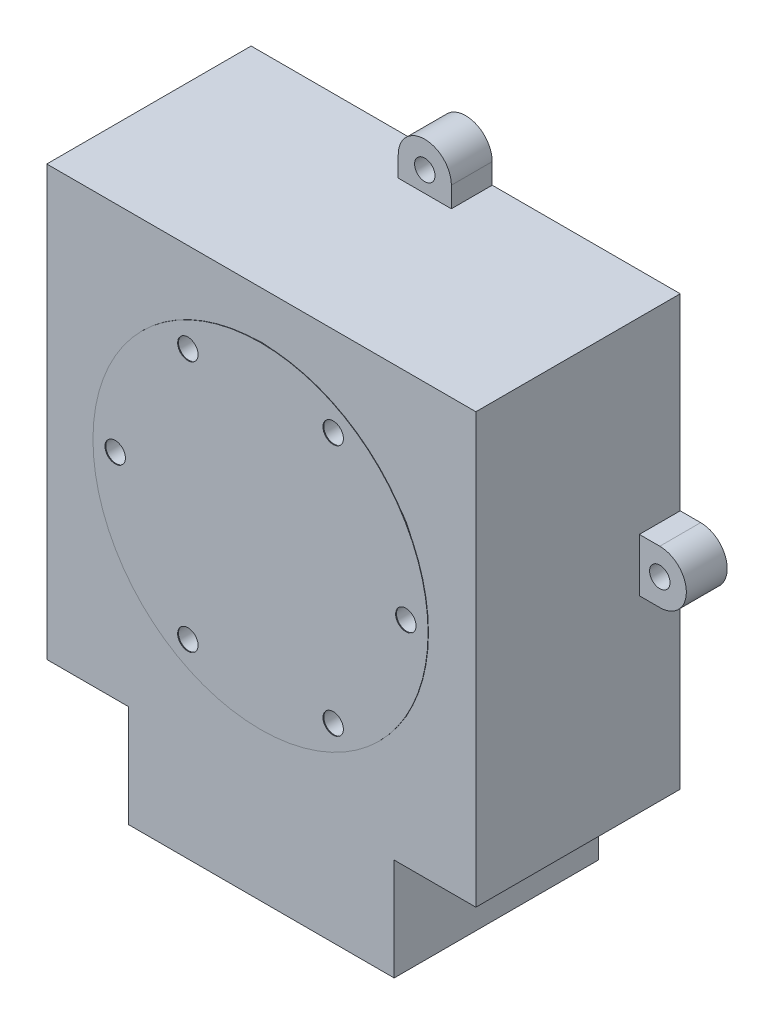
SolidWorks part; units mm, degrees
ref_plane "Front Plane" through (0, 0, 0) normal (0, 0, 1) x (1, 0, 0)
ref_plane "Top Plane" through (0, 0, 0) normal (0, 1, 0) x (1, 0, 0)
ref_plane "Right Plane" through (0, 0, 0) normal (1, 0, 0) x (0, 0, -1)
sketch "Sketch1" plane through (0, 0, 0) normal (0, 0, 1) x (1, 0, 0)
  circle A0 centre (0, 0) radius 41
  dimension "D1" = 82
extrude "Boss-Extrude1" add sketch "Sketch1" along normal blind 0.1 contours A0
sketch "Sketch2" plane through (0, 0, 0) normal (0, 0, -1) x (-1, 0, 0)
  line L0 (-35.56, 0) -> (35.56, 0) construction
  line L1 (0, 0) -> (0, -41) construction
  line L2 (0, 0) -> (0, 41) construction
  line L3 (0, -30.7959) -> (17.78, -30.7959) construction
  line L4 (0, -30.7959) -> (-17.78, -30.7959) construction
  circle A0 centre (-35.56, 0) radius 2.5
  circle A1 centre (35.56, 0) radius 2.5
  circle A2 centre (0, 0) radius 38.06 construction
  circle A3 centre (0, 0) radius 33.06 construction
  circle A4 centre (-17.78, -30.7959) radius 2.5
  circle A5 centre (17.78, -30.7959) radius 2.5
  circle A6 centre (0, 0) radius 41 construction
  circle A7 centre (-17.78, 30.7959) radius 2.5
  circle A8 centre (17.78, 30.7959) radius 2.5
  point P4 (0, 0)
  dimension "D2" = 5
  dimension "D3" = 66.12
  dimension "D4" = 76.12
  dimension "D6" = 5
  dimension "D7" = 5
  dimension "D1" = 71.12
  dimension "D5" = 35.56
extrude "Cut-Extrude1" cut sketch "Sketch2" against normal blind 10
sketch "Sketch3" plane through (0, 0, 0) normal (0, 0, -1) x (-1, 0, 0)
  circle A1 centre (0, 0) radius 47.5 construction
  arc A2 (22.2693, -27.7235) -> (12.8746, -33.1475) centre (17.78, -30.7959) ccw
  circle A3 centre (0, 0) radius 42.5 construction
  arc A5 (-12.8746, -33.1475) -> (-22.2693, -27.7235) centre (-17.78, -30.7959) ccw
  circle A12 centre (0, 0) radius 41
  arc A13 (-35.1439, -5.4241) -> (-35.1439, 5.4241) centre (-35.56, 0) ccw
  arc A14 (-22.2693, 27.7235) -> (-12.8746, 33.1475) centre (-17.78, 30.7959) ccw
  arc A15 (12.8746, 33.1475) -> (22.2693, 27.7235) centre (17.78, 30.7959) ccw
  arc A16 (35.1439, 5.4241) -> (35.1439, -5.4241) centre (35.56, 0) ccw
  arc A17 (22.2693, -27.7235) -> (35.1439, -5.4241) centre (22.9665, -13.2597) ccw
  circle A19 centre (0, 0) radius 41 construction
  arc A25 (-22.2693, 27.7235) -> (-35.1439, 5.4241) centre (-22.9665, 13.2597) ccw
  arc A26 (35.1439, 5.4241) -> (22.2693, 27.7235) centre (22.9665, 13.2597) ccw
  arc A28 (-35.1439, -5.4241) -> (-22.2693, -27.7235) centre (-22.9665, -13.2597) ccw
  arc A29 (-12.8746, -33.1475) -> (12.8746, -33.1475) centre (0, -26.5195) ccw
  arc A30 (12.8746, 33.1475) -> (-12.8746, 33.1475) centre (0, 26.5195) ccw
  dimension "D1" = 95
  dimension "D2" = 85
extrude "Boss-Extrude3" add sketch "Sketch3" along normal blind 0.1 contours A15 A30 A14 A25 A13 A28 A5 A29 A2 A17 A16 A26 region at (0, 0, 0)
sketch "Sketch4" plane through (0, 0, -0.1) normal (0, 0, -1) x (-1, 0, 0)
  line L1 (-52.5, 52.5) -> (52.5, 52.5)
  line L2 (-52.5, 52.5) -> (-52.5, -52.5)
  line L3 (-52.5, -52.5) -> (52.5, -52.5)
  line L4 (52.5, 52.5) -> (52.5, -52.5)
  dimension "D1" = 52.5
  dimension "D2" = 52.5
  dimension "D3" = 52.5
  dimension "D4" = 52.5
extrude "Boss-Extrude4" add sketch "Sketch4" along normal blind 10
sketch "Sketch5" plane through (0, 0, -10.1) normal (0, 0, -1) x (-1, 0, 0)
  line L1 (-52.5, 52.5) -> (52.5, 52.5)
  line L2 (-52.5, 52.5) -> (-52.5, -52.5)
  line L3 (-52.5, -52.5) -> (52.5, -52.5)
  line L4 (52.5, 52.5) -> (52.5, -52.5)
  line L5 (-48.5, 48.5) -> (48.5, 48.5)
  line L6 (-48.5, 48.5) -> (-48.5, -48.5)
  line L7 (-48.5, -48.5) -> (48.5, -48.5)
  line L8 (48.5, 48.5) -> (48.5, -48.5)
  dimension "D1" = 4
  dimension "D2" = 4
  dimension "D3" = 4
  dimension "D4" = 4
extrude "Boss-Extrude5" add sketch "Sketch5" along normal blind 40
sketch "Sketch7" plane through (0, 0, -50.1) normal (0, 0, -1) x (-1, 0, 0)
  line L1 (-48.5, 48.5) -> (48.5, 48.5)
  line L2 (-48.5, 48.5) -> (-48.5, -48.5)
  line L3 (-48.5, -48.5) -> (48.5, -48.5)
  line L4 (48.5, 48.5) -> (48.5, -48.5)
  line L5 (-52.5, 52.5) -> (52.5, 52.5)
  line L6 (-52.5, 52.5) -> (-52.5, -52.5)
  line L7 (-52.5, -52.5) -> (52.5, -52.5)
  line L8 (52.5, 52.5) -> (52.5, -52.5)
extrude "Boss-Extrude6" add sketch "Sketch7" against normal up to surface (50 mm away) up to face at (0, 0, -0.1)
sketch "Sketch8" plane through (0, 0, -50.1) normal (0, 0, -1) x (-1, 0, 0)
  line L0 (-48.5, -48.5) -> (48.5, -48.5) construction
  line L1 (48.5, -48.5) -> (48.5, 48.5) construction
  line L2 (-48.5, 48.5) -> (-48.5, -48.5) construction
  line L3 (48.5, 48.5) -> (-48.5, 48.5) construction
  line L4 (-53, 0) -> (-48.5, 0) construction
  line L5 (-48.5, 48.5) -> (-48.5, -48.5) construction
  line L6 (0, 48.5) -> (0, 53) construction
  line L7 (48.5, 0) -> (53, 0) construction
  line L8 (0, -48.5) -> (0, -53) construction
  line L9 (-48.5, -48.5) -> (48.5, -48.5) construction
  circle A0 centre (-47, 0) radius 2
  circle A1 centre (50.75, 0) radius 2
  circle A2 centre (0, 50.75) radius 2
  circle A3 centre (0, -50.75) radius 2
  circle A4 centre (-47, 0) radius 6 construction
  circle A5 centre (0, 50.75) radius 2.25 construction
  circle A6 centre (0, 0) radius 53 construction
  circle A7 centre (50.75, 0) radius 2.25 construction
  circle A8 centre (0, -50.75) radius 2.25 construction
  parabola Q1 (-50, 50) -> (-50, -50) focus (155.3333, 0) apex (-53, 0) construction
  parabola Q3 (50, 50) -> (-50, 50) focus (0, -155.3333) apex (0, 53) construction
  parabola Q4 (50, -50) -> (50, 50) focus (-155.3333, 0) apex (53, 0) construction
  parabola Q5 (-50, -50) -> (50, -50) focus (0, 155.3333) apex (0, -53) construction
  point P10 (0, -48.5)
  point P13 (48.5, 0)
  point P16 (-48.5, 0)
  point P19 (0, 48.5)
  point P50 (0, -50.75)
  point P51 (50.75, 0)
  point P52 (0, 50.75)
  dimension "D1" = 106
  dimension "D2" = 4
  dimension "D3" = 4
  dimension "D4" = 4
  dimension "D5" = 4
  dimension "D6" = 6
sketch "Sketch11" plane through (0, 0, -10.1) normal (0, 0, -1) x (-1, 0, 0)
  line L2 (0, 38.5) -> (0, 48.5) construction
  line L3 (-39, 38.5) -> (39, 38.5) construction
  line L4 (-39, 38.5) -> (-39, -38.5) construction
  line L5 (-39, -38.5) -> (39, -38.5) construction
  line L6 (39, 38.5) -> (39, -38.5) construction
  line L7 (0, -38.5) -> (0, -48.5) construction
  line L8 (-48.5, -48.5) -> (48.5, -48.5) construction
  line L9 (-39, 0) -> (-48.5, 0) construction
  line L10 (-48.5, 48.5) -> (-48.5, -48.5) construction
  line L11 (39, 0) -> (48.5, 0) construction
  line L12 (48.5, -48.5) -> (48.5, 48.5) construction
  circle A0 centre (-35, 34.5) radius 2
  circle A1 centre (37, 20.5) radius 2
  circle A2 centre (28.5, -36.5) radius 2
  circle A3 centre (-35, -21.5) radius 2
  circle A4 centre (-35, -21.5) radius 5
  circle A5 centre (28.5, -36.5) radius 5
  circle A6 centre (37, 20.5) radius 5
  circle A7 centre (-35, 34.5) radius 5
  dimension "D1" = 4
  dimension "D2" = 72
  dimension "D3" = 57
  dimension "D9" = 4
  dimension "D10" = 4
  dimension "D4" = 4
  dimension "D5" = 63.5
  dimension "D6" = 56
  dimension "D7" = 4
  dimension "D8" = 14
extrude "Boss-Extrude7" add sketch "Sketch11" along normal blind 25
sketch "Sketch10" plane through (0, 0, 0.1) normal (0, 0, 1) x (1, 0, 0)
  circle A0 centre (-17.78, 30.7959) radius 2.5
  circle A1 centre (17.78, 30.7959) radius 2.5
  circle A2 centre (35.56, 0) radius 2.5
  circle A3 centre (17.78, -30.7959) radius 2.5
  circle A4 centre (-17.78, -30.7959) radius 2.5
  circle A5 centre (-35.56, 0) radius 2.5
extrude "Cut-Extrude3" cut sketch "Sketch10" against normal through all
sketch "Sketch13" plane through (0, -52.5, 0) normal (0, -1, 0) x (1, 0, 0)
  line L0 (-53, -50.1) -> (53, -50.1) construction
  line L1 (-32.5, -0.1) -> (32.5, -0.1)
  line L2 (-32.5, -0.1) -> (-32.5, -50.1)
  line L3 (-32.5, -50.1) -> (32.5, -50.1)
  line L4 (32.5, -0.1) -> (32.5, -50.1)
  line L5 (52.5, -50.1) -> (52.5, -0.1) construction
  line L7 (-52.5, -50.1) -> (-52.5, -0.1) construction
  line L8 (52.5, -0.1) -> (-52.5, -0.1) construction
  dimension "D1" = 20
  dimension "D2" = 20
extrude "Boss-Extrude8" add sketch "Sketch13" along normal blind 25
sketch "Sketch14" plane through (0, 0, -50.1) normal (0, 0, -1) x (-1, 0, 0)
  line L1 (-28.5, -48.5) -> (28.5, -48.5)
  line L2 (-28.5, -48.5) -> (-28.5, -73.5)
  line L3 (-28.5, -73.5) -> (28.5, -73.5)
  line L4 (28.5, -48.5) -> (28.5, -73.5)
  line L5 (32.5, -77.5) -> (32.5, -52.5) construction
  line L8 (-32.5, -77.5) -> (-32.5, -52.5) construction
  line L9 (32.5, -77.5) -> (-32.5, -77.5) construction
  dimension "D1" = 4
  dimension "D2" = 4
  dimension "D3" = 4
extrude "Cut-Extrude4" cut sketch "Sketch14" against normal up to surface (40 mm away) up to face at (-38.06, 0, -10.1)
sketch "Sketch15" plane through (0, 0, -50.1) normal (0, 0, -1) x (-1, 0, 0)
  line L4 (32.5, -77.5) -> (32.5, -52.5) construction
  line L5 (32.5, -52.5) -> (52.5, -52.5) construction
  line L6 (-52.5, -52.5) -> (-32.5, -52.5) construction
  line L7 (-32.5, -77.5) -> (-32.5, -52.5) construction
  line L8 (-37.5, -64) -> (-32.5, -64)
  line L9 (-44, -57.5) -> (-44, -52.5)
  line L10 (-44, -52.5) -> (-32.5, -52.5)
  line L11 (-32.5, -52.5) -> (-32.5, -64)
  line L12 (44, -57.5) -> (44, -52.5)
  line L13 (44, -52.5) -> (32.5, -52.5)
  line L14 (32.5, -52.5) -> (32.5, -64)
  line L15 (32.5, -64) -> (37.5, -64)
  circle A0 centre (37.5, -57.5) radius 2.5
  circle A1 centre (-37.5, -57.5) radius 2.5
  arc A2 (-44, -57.5) -> (-37.5, -64) centre (-37.5, -57.5) ccw
  arc A3 (37.5, -64) -> (44, -57.5) centre (37.5, -57.5) ccw
  point P5 (33.8195, -53.6617)
  dimension "D1" = 4
  dimension "D2" = 4
  dimension "D3" = 5
  dimension "D4" = 5
  dimension "5" = 5
  dimension "D5" = 5
  dimension "D6" = 5
  dimension "D7" = 5
extrude "Boss-Extrude9" add sketch "Sketch15" against normal blind 10
sketch "Sketch16" plane through (0, 0, -50.1) normal (0, 0, -1) x (-1, 0, 0)
  line L0 (-57.5, 6.5) -> (-48.5, 6.5)
  line L1 (-48.5, 48.5) -> (-48.5, -48.5) construction
  line L2 (-48.5, 6.5) -> (-48.5, -6.5)
  line L3 (-48.5, 48.5) -> (-48.5, -48.5) construction
  line L4 (-48.5, -6.5) -> (-57.5, -6.5)
  line L5 (57.5, 6.5) -> (48.5, 6.5)
  line L6 (48.5, -48.5) -> (48.5, 48.5) construction
  line L7 (57.5, -6.5) -> (48.5, -6.5)
  line L8 (48.5, -48.5) -> (48.5, 48.5) construction
  line L9 (52.5, -52.5) -> (52.5, 52.5) construction
  line L10 (52.5, 52.5) -> (-52.5, 52.5) construction
  line L12 (48.5, -6.5) -> (48.5, 6.5)
  line L14 (-6.5, 57.5) -> (-6.5, 48.5)
  line L16 (48.5, 48.5) -> (-48.5, 48.5) construction
  line L17 (6.5, 48.5) -> (6.5, 57.5)
  line L18 (48.5, 48.5) -> (-48.5, 48.5) construction
  line L19 (-6.5, 48.5) -> (6.5, 48.5)
  line L20 (-52.5, 52.5) -> (-52.5, -52.5) construction
  circle A0 centre (-57.5, 0) radius 2.5
  circle A1 centre (57.5, 0) radius 2.5
  arc A2 (57.5, -6.5) -> (57.5, 6.5) centre (57.5, 0) ccw
  arc A3 (-57.5, 6.5) -> (-57.5, -6.5) centre (-57.5, 0) ccw
  circle A4 centre (0, 57.5) radius 2.5
  arc A5 (6.5, 57.5) -> (-6.5, 57.5) centre (0, 57.5) ccw
  point P24 (-48.5, 0)
  dimension "D1" = 5
  dimension "D2" = 5
  dimension "D3" = 4
  dimension "D4" = 4
  dimension "D5" = 4
  dimension "D6" = 5
  dimension "D9" = 5
  dimension "D7" = 5
  dimension "D8" = 5
extrude "Boss-Extrude10" add sketch "Sketch16" against normal blind 10
